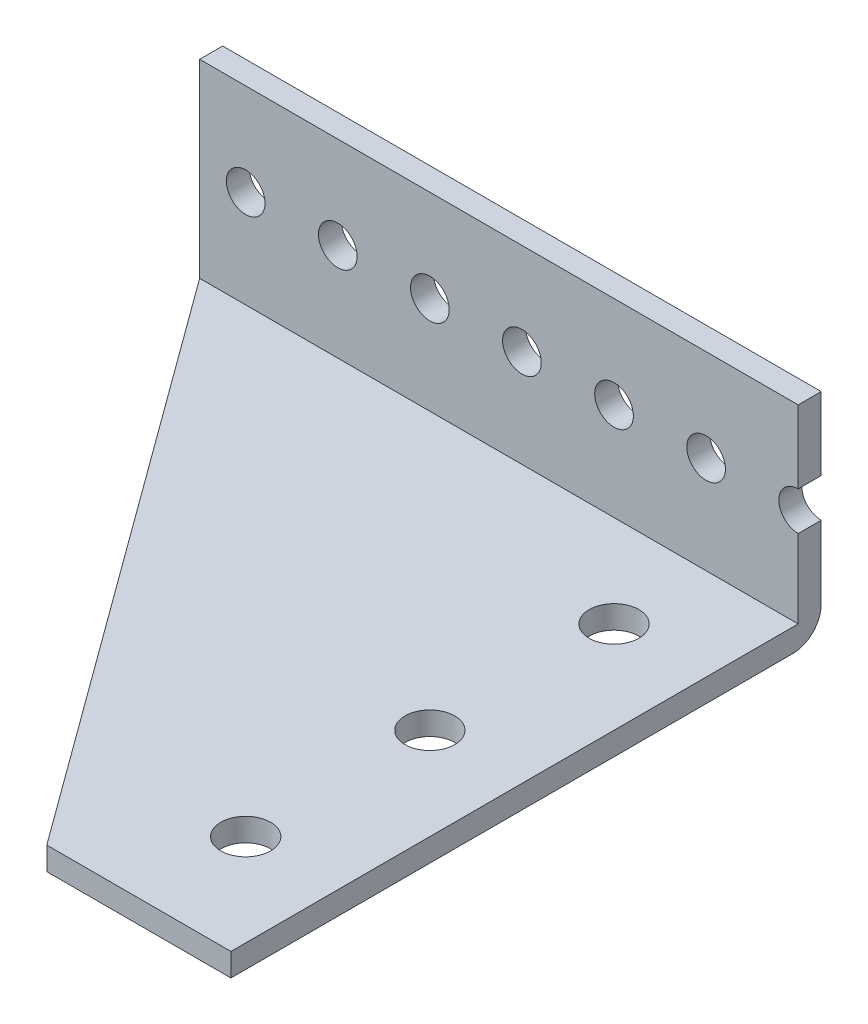
SolidWorks part; units mm, degrees
ref_plane "Front Plane" through (0, 0, 0) normal (0, 0, 1) x (1, 0, 0)
ref_plane "Top Plane" through (0, 0, 0) normal (0, 1, 0) x (1, 0, 0)
ref_plane "Right Plane" through (0, 0, 0) normal (1, 0, 0) x (0, 0, -1)
sketch "Sketch1" plane through (0, 0, 0) normal (0, 1, 0) x (1, 0, 0)
  line L0 (41.275, -40.7035) -> (41.275, 40.7035)
  line L1 (41.275, 40.7035) -> (-41.275, 40.7035)
  line L3 (-41.275, -40.7035) -> (-41.275, 40.7035)
  line L4 (-41.275, -40.7035) -> (41.275, -40.7035)
  line L5 (41.275, 40.7035) -> (-41.275, -40.7035) construction
  line L6 (0, -55) -> (0, 55) construction
  line L7 (-55, 0) -> (55, 0) construction
  point P2 (0, 0)
  dimension "D2" = 81.407
  dimension "D1" = 82.55
extrude "Boss-Extrude1" add sketch "Sketch1" along normal blind 3.175 from offset 34.925 offset against normal yes
sketch "Sketch3" plane through (0, -31.75, 0) normal (0, 1, 0) x (1, 0, 0)
  line L0 (41.275, 37.5285) -> (-41.275, 37.5285)
  line L1 (-41.275, 37.5285) -> (-41.275, 40.7035)
  line L2 (-41.275, 40.7035) -> (41.275, 40.7035)
  line L4 (41.275, 37.5285) -> (41.275, 40.7035)
  line L5 (-41.275, 40.7035) -> (-41.275, -40.7035) construction
  line L6 (41.275, -40.7035) -> (41.275, 40.7035) construction
  line L7 (41.275, 40.7035) -> (-41.275, 40.7035) construction
  dimension "D1" = 3.175
extrude "Boss-Extrude2" add sketch "Sketch3" along normal blind 50.8
hole_wizard "#10 Clearance Hole2" positions "Sketch7" profile "Sketch6" hole size "#10" standard "ANSI Inch" end condition through all
sketch "Sketch7" plane through (0, 0, -40.7035) normal (0, 0, -1) x (-1, 0, 0)
  line L2 (-41.275, -18.288) -> (34.925, -18.288) construction
  line L5 (-41.275, 7.112) -> (34.925, 7.112) construction
  line L8 (41.275, 19.05) -> (41.275, -34.925) construction
  line L9 (-41.275, 19.05) -> (-41.275, -34.925) construction
  line L10 (-41.275, 19.05) -> (41.275, 19.05) construction
  point P56 (22.225, 7.112)
  point P57 (9.525, 7.112)
  point P58 (-3.175, 7.112)
  point P59 (-15.875, 7.112)
  point P61 (-28.575, 7.112)
  point P118 (22.225, -18.288)
  point P119 (9.525, -18.288)
  point P120 (-3.175, -18.288)
  point P121 (-15.875, -18.288)
  point P123 (-28.575, -18.288)
  point P157 (34.925, 7.112)
  point P159 (34.925, -18.288)
  point P185 (-41.275, 7.112)
  point P189 (-41.275, -18.288)
  dimension "D1" = 6.35
  dimension "D2" = 11.938
  dimension "D3" = 12.7
  dimension "D4" = 25.4
  dimension "D5" = 12.7
  dimension "D6" = 12.7
  dimension "D7" = 12.7
  dimension "D8" = 12.7
  dimension "D10" = 12.7
sketch "Sketch6" plane through (-22.225, 7.112, -40.7035) normal (1, 0, 0) x (0, 1, 0)
  line L0 (0, 0) -> (0, 81.407)
  line L1 (0, 81.407) -> (2.667, 81.407)
  line L2 (2.667, 81.407) -> (2.667, 0)
  line L5 (2.667, 0) -> (0, 0)
  line L11 (0, -6.35) -> (0, 107.95) construction
  dimension "Thru Hole Dia." = 5.334
  dimension "Thru Hole Depth" = 81.407
chamfer "Chamfer1" distance 3.175 angle 45 1 edges at (-41.275, 19.05, -39.116)
fillet "Fillet2" radius 3.937 1 edges at (0, -34.925, -40.7035) tangent propagation no
sketch "Sketch9" plane through (0, -34.925, 0) normal (0, -1, 0) x (1, 0, 0)
  line L2 (41.275, -40.7035) -> (-41.275, -40.7035) construction
  line L3 (41.275, 40.7035) -> (41.275, -36.7665) construction
  line L5 (-41.275, -37.5285) -> (-41.275, 40.7035)
  line L6 (-41.275, 40.7035) -> (41.275, 40.7035) construction
  line L7 (28.575, -40.7035) -> (28.575, 40.7035) construction
  line L10 (-41.275, -37.5285) -> (15.875, 40.7035)
  line L11 (15.875, 40.7035) -> (-41.275, 40.7035)
  line L12 (41.275, 40.7035) -> (41.275, -36.7665) construction
  line L14 (-41.275, -36.7665) -> (-41.275, 40.7035) construction
  line L16 (-41.275, -37.5285) -> (41.275, -37.5285) construction
  circle A0 centre (34.925, 1.4605) radius 3.429 construction
  circle A1 centre (34.925, -11.2395) radius 3.429 construction
  circle A2 centre (34.925, -23.9395) radius 3.429 construction
  circle A3 centre (28.575, -24.8285) radius 3.429
  circle A7 centre (28.575, 0.5715) radius 3.429
  circle A8 centre (28.575, 25.9715) radius 3.429
  dimension "D3" = 6.858
  dimension "D7" = 16.764
  dimension "D9" = 6.858
  dimension "D10" = 0
  dimension "D11" = 3
  dimension "D12" = 25.4
  dimension "D2" = 12.7
  dimension "D4" = 12.7
  dimension "D5" = 12.7
  dimension "D6" = 6.35
  dimension "D8" = 25.4
  dimension "D13" = 12.7
extrude "Cut-Extrude2" cut sketch "Sketch9" against normal through all
sketch "Sketch10" plane through (0, 0, -40.7035) normal (0, 0, -1) x (-1, 0, 0)
  line L0 (-41.275, -5.588) -> (41.275, -5.588)
  line L1 (-41.275, 4.445) -> (-41.275, -15.621) construction
  line L2 (41.275, 15.875) -> (41.275, -30.988) construction
  line L3 (41.275, -5.588) -> (41.275, 19.05)
  line L4 (41.275, 19.05) -> (-41.275, 19.05)
  line L5 (-41.275, 19.05) -> (-41.275, -5.588)
  point P6 (0, 0)
  point P11 (-41.275, -4.944)
extrude "Cut-Extrude3" cut sketch "Sketch10" against normal through all
